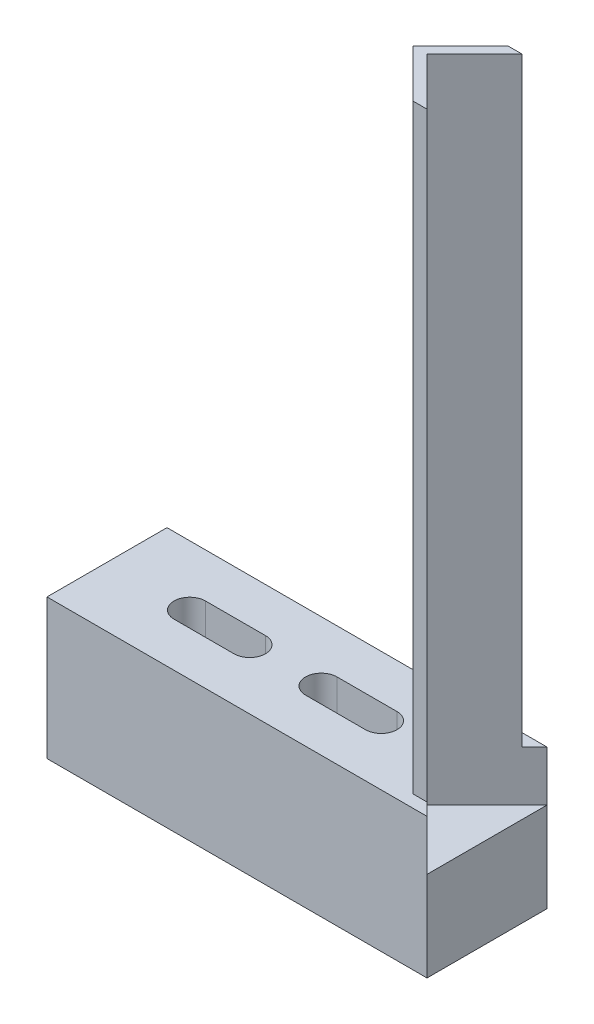
SolidWorks part; units mm, degrees
ref_plane "Front Plane" through (0, 0, 0) normal (0, 0, 1) x (1, 0, 0)
ref_plane "Top Plane" through (0, 0, 0) normal (0, 1, 0) x (1, 0, 0)
ref_plane "Right Plane" through (0, 0, 0) normal (1, 0, 0) x (0, 0, -1)
sketch "Sketch1" plane through (0, 0, 0) normal (0, 0, 1) x (1, 0, 0)
  line L0 (0, 0) -> (48.26, 0)
  line L6 (0, 0) -> (0, 17.78)
  line L10 (0, 17.78) -> (48.26, 17.78)
  line L11 (48.26, 0) -> (48.26, 17.78)
  dimension "D1" = 48.26
  dimension "D2" = 17.78
extrude "Boss-Extrude1" add sketch "Sketch1" against normal blind 15.24
sketch "Sketch3" plane through (0, 17.78, 0) normal (0, 1, 0) x (1, 0, 0)
  line L0 (48.26, 15.24) -> (40.64, 7.62)
  line L1 (40.64, 7.62) -> (48.26, 0)
  line L2 (44.8897, 13.6658) -> (38.8439, 7.62)
  line L4 (48.26, 15.24) -> (48.26, 0)
  line L5 (38.8439, 7.62) -> (44.8897, 1.5742)
  line L9 (44.8897, 13.6658) -> (46.6858, 13.6658)
  line L11 (44.8897, 1.5742) -> (46.6858, 1.5742)
  line L12 (48.26, 0) -> (0, 0) construction
  line L13 (48.26, 15.24) -> (0, 15.24) construction
  line M1 (0, 0) -> (48.26, 0)
  line M2 (48.26, 0) -> (48.26, 15.24)
  line M3 (48.26, 15.24) -> (0, 15.24)
  dimension "D1" = 90
  dimension "D2" = 90
  dimension "D3" = 8.55
  dimension "D4" = 8.55
  dimension "D6" = 1.27
extrude "Cut-Extrude1" cut sketch "Sketch3" against normal blind 6.38 contours L0 L1 M2 region at (45.72, 17.78, -7.62)
sketch "Sketch4" plane through (0, 17.78, 0) normal (0, 1, 0) x (1, 0, 0)
  line L0 (34.83, 7.62) -> (27.21, 7.62) construction
  line L1 (34.83, 5.62) -> (27.21, 5.62)
  line L2 (34.83, 9.62) -> (27.21, 9.62)
  line L3 (18.13, 7.62) -> (10.51, 7.62) construction
  line L4 (18.13, 5.62) -> (10.51, 5.62)
  line L5 (18.13, 9.62) -> (10.51, 9.62)
  line L6 (48.26, 0) -> (0, 0) construction
  arc A0 (34.83, 5.62) -> (34.83, 9.62) centre (34.83, 7.62) ccw
  arc A1 (27.21, 9.62) -> (27.21, 5.62) centre (27.21, 7.62) ccw
  arc A2 (18.13, 5.62) -> (18.13, 9.62) centre (18.13, 7.62) ccw
  arc A3 (10.51, 9.62) -> (10.51, 5.62) centre (10.51, 7.62) ccw
  point P2 (31.02, 7.62)
  point P7 (14.32, 7.62)
  point P14 (36.83, 7.62)
  point P16 (8.51, 7.62)
  point P18 (20.13, 7.62)
  point P19 (25.21, 7.62)
  dimension "D1" = 4
  dimension "D2" = 3.81
  dimension "D3" = 7.62
  dimension "D4" = 7.62
  dimension "D5" = 5.08
extrude "Cut-Extrude2" cut sketch "Sketch4" against normal through all
extrude "Boss-Extrude2" add sketch "Sketch3<3>" along normal blind 76.2 contours L2 L5 L1 L0 M1 M3 region at (43.561, 17.78, -10.7448)
sketch "Sketch3<3>" plane through (0, 17.78, 0) normal (0, 1, 0) x (1, 0, 0) same geometry as "Sketch3"
